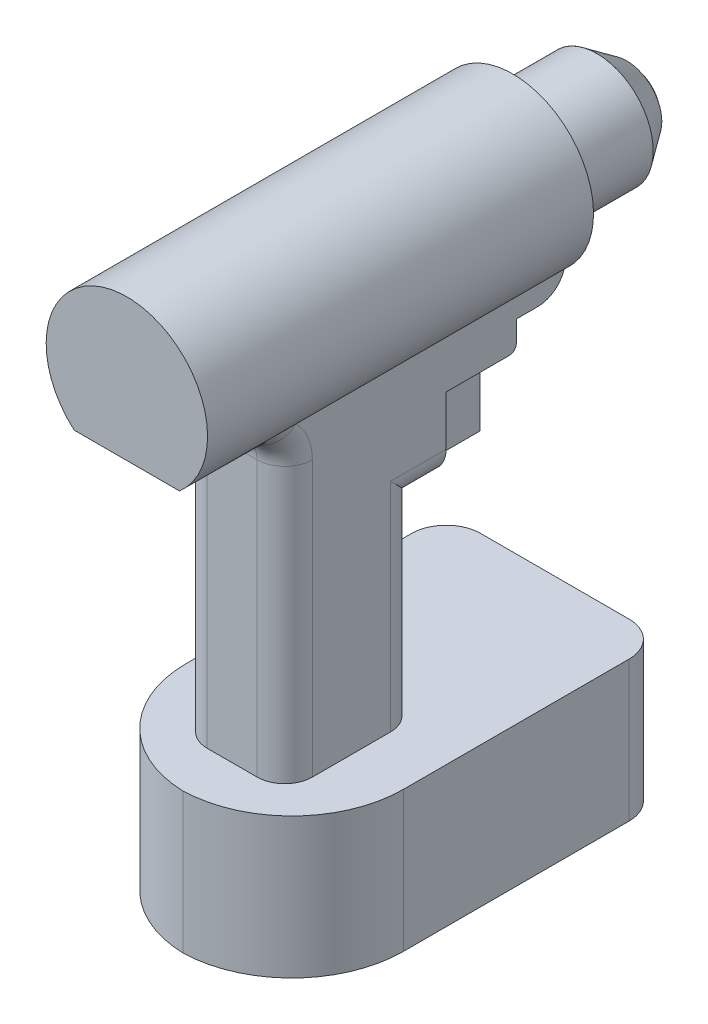
SolidWorks part; units mm, degrees
ref_plane "Front Plane" through (0, 0, 0) normal (0, 0, 1) x (1, 0, 0)
ref_plane "Top Plane" through (0, 0, 0) normal (0, 1, 0) x (1, 0, 0)
ref_plane "Right Plane" through (0, 0, 0) normal (1, 0, 0) x (0, 0, -1)
sketch "Sketch1" plane through (0, 0, 0) normal (0, 1, 0) x (1, 0, 0)
  line L1 (-39.37, -67.31) -> (39.37, -67.31)
  line L2 (-39.37, -67.31) -> (-39.37, 67.31)
  line L3 (-39.37, 67.31) -> (39.37, 67.31)
  line L4 (39.37, -67.31) -> (39.37, 67.31)
  line L5 (-39.37, -67.31) -> (39.37, 67.31) construction
  line L6 (-39.37, 67.31) -> (39.37, -67.31) construction
  point P0 (0, 0)
  dimension "D1" = 134.62
  dimension "D2" = 78.74
extrude "Boss-Extrude1" add sketch "Sketch1" along normal blind 50.8
sketch "Sketch2" plane through (0, 50.8, 0) normal (0, 1, 0) x (1, 0, 0)
  line L0 (-39.37, -1.27) -> (39.37, -1.27) construction
  line L1 (-39.37, 67.31) -> (-39.37, -67.31) construction
  line L2 (39.37, -67.31) -> (39.37, 67.31) construction
  line L3 (39.37, 67.31) -> (-39.37, 67.31) construction
  line L4 (-39.37, -49.53) -> (39.37, -49.53) construction
  line L5 (-39.37, -67.31) -> (39.37, -67.31) construction
  line L6 (0, 67.31) -> (0, -83.0167) construction
  line L7 (-39.37, -1.27) -> (-39.37, -49.53) construction
  line L8 (-39.37, -25.4) -> (39.37, -25.4) construction
  line L10 (-19.05, -49.53) -> (19.05, -49.53)
  line L11 (-19.05, -49.53) -> (-19.05, -1.27)
  line L12 (-19.05, -1.27) -> (19.05, -1.27)
  line L13 (19.05, -49.53) -> (19.05, -1.27)
  line L14 (-19.05, -49.53) -> (19.05, -1.27) construction
  line L15 (-19.05, -1.27) -> (19.05, -49.53) construction
  point P17 (0, -25.4)
  dimension "D1" = 68.58
  dimension "D2" = 17.78
  dimension "D3" = 38.1
extrude "Boss-Extrude2" add sketch "Sketch2" along normal blind 106.68
sketch "Sketch3" plane through (0, 157.48, 0) normal (0, 1, 0) x (1, 0, 0)
  line L0 (19.05, -49.53) -> (19.05, -1.27) construction
  line L1 (-19.05, -49.53) -> (19.05, -49.53)
  line L2 (-19.05, -49.53) -> (-19.05, 21.59)
  line L3 (-19.05, 21.59) -> (19.05, 21.59)
  line L4 (19.05, -49.53) -> (19.05, 21.59)
  line L6 (-19.05, -49.53) -> (19.05, -49.53)
  line L7 (-19.05, -49.53) -> (-19.05, -87.63)
  line L8 (-19.05, -87.63) -> (19.05, -87.63)
  line L9 (19.05, -49.53) -> (19.05, -87.63)
  line M6 (19.05, -49.53) -> (19.05, -1.27)
  line M7 (19.05, -1.27) -> (-19.05, -1.27)
  line M8 (-19.05, -1.27) -> (-19.05, -49.53)
  line M9 (-19.05, -49.53) -> (19.05, -49.53)
  dimension "D1" = 71.12
  dimension "D2" = 38.1
extrude "Boss-Extrude3" add sketch "Sketch3" along normal blind 58.42 contours L9 L7 L8 M9 | M9 M6 M7 M8 | L4 L3 L2 M7 region at (0, 157.48, 25.4) region at (0, 157.48, 68.58) region at (0, 157.48, -10.16)
sketch "Sketch4" plane through (19.05, 0, 0) normal (1, 0, 0) x (0, 0, -1)
  line L0 (-49.53, 157.48) -> (-87.63, 157.48) construction
  line L1 (21.59, 157.48) -> (-1.27, 157.48) construction
  line L2 (21.59, 215.9) -> (21.59, 157.48) construction
  line L3 (-87.63, 215.9) -> (-87.63, 157.48) construction
  line L4 (21.59, 215.9) -> (-87.63, 215.9) construction
  line L5 (-49.53, 157.48) -> (-87.63, 157.48)
  line L6 (21.59, 157.48) -> (-1.27, 157.48)
  line L7 (21.59, 215.9) -> (21.59, 157.48)
  line L8 (-87.63, 215.9) -> (-87.63, 157.48)
  line L9 (21.59, 215.9) -> (-87.63, 215.9)
  line L10 (-49.53, 157.48) -> (-1.27, 157.48)
extrude "Boss-Extrude4" add sketch "Sketch4" along normal blind 7.62
sketch "Sketch5" plane through (-19.05, 0, 0) normal (-1, 0, 0) x (0, 0, 1)
  line L0 (87.63, 215.9) -> (87.63, 157.48) construction
  line L1 (49.53, 157.48) -> (87.63, 157.48) construction
  line L2 (-21.59, 157.48) -> (1.27, 157.48) construction
  line L3 (-21.59, 215.9) -> (-21.59, 157.48) construction
  line L4 (-21.59, 215.9) -> (87.63, 215.9) construction
  line L5 (87.63, 215.9) -> (87.63, 157.48)
  line L6 (49.53, 157.48) -> (87.63, 157.48)
  line L7 (-21.59, 157.48) -> (1.27, 157.48)
  line L8 (-21.59, 215.9) -> (-21.59, 157.48)
  line L9 (-21.59, 215.9) -> (87.63, 215.9)
  line L10 (1.27, 157.48) -> (49.53, 157.48)
extrude "Boss-Extrude5" add sketch "Sketch5" along normal blind 7.62
sketch "Sketch6" plane through (0, 0, -21.59) normal (0, 0, -1) x (-1, 0, 0)
  line L0 (0, 215.9) -> (0, 157.48) construction
  line L1 (26.67, 215.9) -> (-26.67, 215.9) construction
  line L2 (26.67, 157.48) -> (-26.67, 157.48) construction
  circle A0 centre (0, 186.69) radius 29.21
  dimension "D1" = 58.42
extrude "Boss-Extrude6" add sketch "Sketch6" along normal blind 30.48
sketch "Sketch7" plane through (0, 0, -21.59) normal (0, 0, 1) x (1, 0, 0)
  line L0 (-26.67, 174.7763) -> (-26.67, 198.6037) construction
  line L1 (26.67, 198.6037) -> (26.67, 174.7763) construction
  line L2 (-26.67, 174.7763) -> (-26.67, 198.6037)
  line L3 (26.67, 198.6037) -> (26.67, 174.7763)
  arc A0 (-26.67, 198.6037) -> (-26.67, 174.7763) centre (0, 186.69) ccw construction
  arc A1 (26.67, 174.7763) -> (26.67, 198.6037) centre (0, 186.69) ccw construction
  arc A2 (-26.67, 198.6037) -> (-26.67, 174.7763) centre (0, 186.69) ccw
  arc A3 (26.67, 174.7763) -> (26.67, 198.6037) centre (0, 186.69) ccw
extrude "Boss-Extrude7" add sketch "Sketch7" along normal up to surface (109.22 mm away) up to face at (0, 186.69, 87.63)
sketch "Sketch8" plane through (0, 0, -21.59) normal (0, 0, -1) x (-1, 0, 0)
  line L0 (-26.67, 174.7763) -> (-26.67, 157.48) construction
  line L1 (-26.67, 157.48) -> (0, 157.48) construction
  line L2 (0, 157.48) -> (26.67, 157.48) construction
  line L3 (26.67, 157.48) -> (26.67, 174.7763) construction
  line L4 (26.67, 198.6037) -> (26.67, 215.9) construction
  line L5 (26.67, 215.9) -> (0, 215.9) construction
  line L6 (0, 215.9) -> (-26.67, 215.9) construction
  line L7 (-26.67, 215.9) -> (-26.67, 198.6037) construction
  line L8 (-26.67, 174.7763) -> (-26.67, 157.48)
  line L9 (-26.67, 157.48) -> (0, 157.48)
  line L10 (0, 157.48) -> (26.67, 157.48)
  line L11 (26.67, 157.48) -> (26.67, 174.7763)
  line L12 (26.67, 198.6037) -> (26.67, 215.9)
  line L13 (26.67, 215.9) -> (0, 215.9)
  line L14 (0, 215.9) -> (-26.67, 215.9)
  line L15 (-26.67, 215.9) -> (-26.67, 198.6037)
  line L16 (-19.05, 157.48) -> (-19.05, 164.5468)
  line L17 (19.05, 157.48) -> (19.05, 164.5468)
  arc A0 (-26.67, 174.7763) -> (0, 157.48) centre (0, 186.69) ccw construction
  arc A1 (0, 157.48) -> (26.67, 174.7763) centre (0, 186.69) ccw construction
  arc A2 (26.67, 198.6037) -> (0, 215.9) centre (0, 186.69) ccw construction
  arc A3 (0, 215.9) -> (-26.67, 198.6037) centre (0, 186.69) ccw construction
  arc A4 (-26.67, 174.7763) -> (0, 157.48) centre (0, 186.69) ccw
  arc A5 (0, 157.48) -> (26.67, 174.7763) centre (0, 186.69) ccw
  arc A6 (26.67, 198.6037) -> (0, 215.9) centre (0, 186.69) ccw
  arc A7 (0, 215.9) -> (-26.67, 198.6037) centre (0, 186.69) ccw
  arc M1 (-26.67, 198.6037) -> (0, 215.9) centre (0, 186.69) cw
  line M2 (0, 215.9) -> (-26.67, 215.9)
  line M3 (-26.67, 215.9) -> (-26.67, 198.6037)
extrude "Cut-Extrude2" cut sketch "Sketch8" against normal through all contours A4 L8 L9 L16 | A5 L17 L10 L11 | A6 L12 L13 | M3 M1 M2 region at (23.4145, 163.5436, -21.59) region at (-23.4145, 163.5436, -21.59) region at (-20.4576, 211.1487, -21.59) region at (20.4576, 211.1487, -21.59)
sketch "Sketch9" plane through (0, 0, -52.07) normal (0, 0, -1) x (-1, 0, 0)
  circle A0 centre (0, 186.69) radius 20.32
  dimension "D1" = 40.64
extrude "Boss-Extrude8" add sketch "Sketch9" along normal blind 30.48
sketch "Sketch10" plane through (0, 0, -82.55) normal (0, 0, -1) x (-1, 0, 0)
  circle A0 centre (0, 186.69) radius 10.16
  dimension "D1" = 20.32
extrude "Boss-Extrude9" add sketch "Sketch10" along normal blind 12.7
sketch "Sketch11" plane through (0, 0, 0) normal (1, 0, 0) x (0, 0, -1)
  line L0 (93.3088, 196.85) -> (93.3088, 199.39)
  line L2 (95.25, 196.85) -> (82.55, 196.85) construction
  line L3 (82.55, 207.01) -> (93.3088, 199.39)
  line L4 (95.25, 186.69) -> (113.8659, 186.69) construction
  line L5 (95.25, 176.53) -> (95.25, 196.85) construction
  line L6 (93.3088, 196.85) -> (82.55, 207.01)
  dimension "D1" = 2.54
  dimension "D2" = 13.1839
revolve "Revolve1" add sketch "Sketch11" angle 360 about L4
sketch "Sketch12" plane through (19.05, 0, 0) normal (1, 0, 0) x (0, 0, -1)
  line L0 (-49.53, 119.38) -> (-1.27, 119.38) construction
  line L1 (-49.53, 157.48) -> (-49.53, 50.8) construction
  line L2 (-1.27, 157.48) -> (-1.27, 50.8) construction
  line L3 (-1.27, 157.48) -> (21.59, 157.48) construction
  line L4 (21.59, 157.48) -> (52.07, 157.48) construction
  line L6 (-1.27, 157.48) -> (34.29, 157.48)
  line L7 (-1.27, 157.48) -> (-1.27, 119.38)
  line L8 (-1.27, 119.38) -> (34.29, 119.38)
  line L9 (34.29, 157.48) -> (34.29, 119.38)
  point P8 (34.29, 157.48)
  dimension "D1" = 38.1
  dimension "D2" = 35.56
sketch "Sketch13" plane through (0, 0, -21.59) normal (0, 0, -1) x (-1, 0, 0)
  line L0 (0, 157.48) -> (19.05, 157.48) construction
  line L1 (19.05, 157.48) -> (19.05, 164.5468) construction
  line L2 (-19.05, 164.5468) -> (-19.05, 157.48) construction
  line L3 (-19.05, 157.48) -> (0, 157.48) construction
  line L4 (0, 157.48) -> (19.05, 157.48)
  line L5 (19.05, 157.48) -> (19.05, 164.5468)
  line L6 (-19.05, 164.5468) -> (-19.05, 157.48)
  line L7 (-19.05, 157.48) -> (0, 157.48)
  arc A0 (0, 157.48) -> (19.05, 164.5468) centre (0, 186.69) ccw construction
  arc A1 (-19.05, 164.5468) -> (0, 157.48) centre (0, 186.69) ccw construction
  arc A2 (0, 157.48) -> (19.05, 164.5468) centre (0, 186.69) ccw
  arc A3 (-19.05, 164.5468) -> (0, 157.48) centre (0, 186.69) ccw
  line M1 (-19.05, 164.5468) -> (-19.05, 157.48)
  line M2 (-19.05, 157.48) -> (0, 157.48)
  arc M3 (0, 157.48) -> (-19.05, 164.5468) centre (0, 186.69) cw
extrude "Boss-Extrude12" add sketch "Sketch13" along normal up to surface (30.48 mm away) contours M3 M1 M2 | A2 L4 L5 region at (-14.4104, 159.5474, -21.59) region at (14.4104, 159.5474, -21.59) up to face at (-20.32, 186.69, -52.07)
extrude "Boss-Extrude13" add sketch "Sketch12" against normal up to surface (38.1 mm away) up to face at (-19.05, 132.5767, 21.59)
sketch "Sketch14" plane through (19.05, 0, 0) normal (1, 0, 0) x (0, 0, -1)
  line L0 (34.29, 119.38) -> (34.29, 157.48) construction
  line L2 (34.29, 157.48) -> (52.07, 157.48) construction
  line L3 (8.89, 147.32) -> (34.29, 147.32)
  line L4 (8.89, 147.32) -> (8.89, 119.38)
  line L5 (8.89, 119.38) -> (34.29, 119.38)
  line L6 (34.29, 119.38) -> (34.29, 147.32)
  line L7 (-1.27, 119.38) -> (34.29, 119.38) construction
  point P0 (34.29, 147.32)
  point P1 (8.89, 147.32)
  point P6 (34.29, 119.38)
  dimension "D1" = 10.16
  dimension "D3" = 25.4
extrude "Cut-Extrude3" cut sketch "Sketch14" against normal through all
sketch "Sketch15" plane through (0, 0, -8.89) normal (0, 0, -1) x (-1, 0, 0)
  line L0 (19.05, 147.32) -> (-19.05, 147.32) construction
  line L1 (-12.7, 147.32) -> (12.7, 147.32)
  line L2 (-12.7, 147.32) -> (-12.7, 119.38)
  line L3 (-12.7, 119.38) -> (12.7, 119.38)
  line L4 (12.7, 147.32) -> (12.7, 119.38)
  line L5 (19.05, 119.38) -> (-19.05, 119.38) construction
  dimension "D1" = 6.35
  dimension "D2" = 6.35
extrude "Boss-Extrude14" add sketch "Sketch15" along normal blind 18.542
sketch "Sketch16" plane through (19.05, 0, 0) normal (1, 0, 0) x (0, 0, -1)
  line L0 (-80.9832, 164.5468) -> (-80.9832, 160.7368)
  line L2 (-87.63, 164.5468) -> (52.07, 164.5468) construction
  line L3 (-87.63, 157.48) -> (-49.53, 157.48)
  line L4 (-80.9832, 164.5468) -> (-87.63, 164.5468)
  line L5 (-87.63, 164.5468) -> (-87.63, 157.48)
  line L6 (-49.53, 157.48) -> (-49.53, 160.02)
  line L7 (-49.53, 160.02) -> (-80.9832, 160.7368)
  dimension "D1" = 3.81
  dimension "D2" = 2.54
  dimension "D3" = 31.4532
extrude "Cut-Extrude4" cut sketch "Sketch16" against normal through all
fillet "Fillet1" radius 10 1 edges at (0, 160.7368, 80.9832)
fillet "Fillet2" radius 10 1 edges at (0, 157.48, -52.07)
fillet "Fillet3" radius 2.54 1 edges at (0, 147.32, -34.29)
fillet "Fillet4" radius 10 2 edges at (-19.05, 85.09, 1.27) (19.05, 85.09, 1.27)
fillet "Fillet5" radius 10 1 edges at (0, 160.02, 49.53)
fillet "Fillet6" radius 10 6 edges at (-19.05, 160.4013, 66.2605) (-19.05, 157.2353, 52.3788) (19.05, 160.4013, 66.2605) (19.05, 157.2353, 52.3788) (-19.05, 100.5226, 49.53) (19.05, 100.5226, 49.53)
fillet "Fillet7" radius 10 2 edges at (-19.05, 119.38, 1.19) (19.05, 119.38, 1.19)
sketch "Sketch17" plane through (12.7, 0, 0) normal (1, 0, 0) x (0, 0, -1)
  line L0 (27.432, 147.32) -> (27.432, 120.0699) construction
  line L3 (8.89, 122.6099) -> (27.432, 122.6099)
  line L5 (8.89, 122.6099) -> (8.89, 116.2085)
  line L6 (8.89, 116.2085) -> (29.0015, 116.2085)
  line L7 (29.0015, 116.2085) -> (29.0015, 122.6099)
  line L8 (29.0015, 122.6099) -> (27.432, 122.6099)
extrude "Cut-Extrude5" cut sketch "Sketch17" against normal through all
fillet "Fillet8" radius 40.48 2 edges at (-39.37, 25.4, 67.31) (39.37, 25.4, 67.31)
fillet "Fillet9" radius 12.54 2 edges at (39.37, 25.4, -67.31) (-39.37, 25.4, -67.31)
